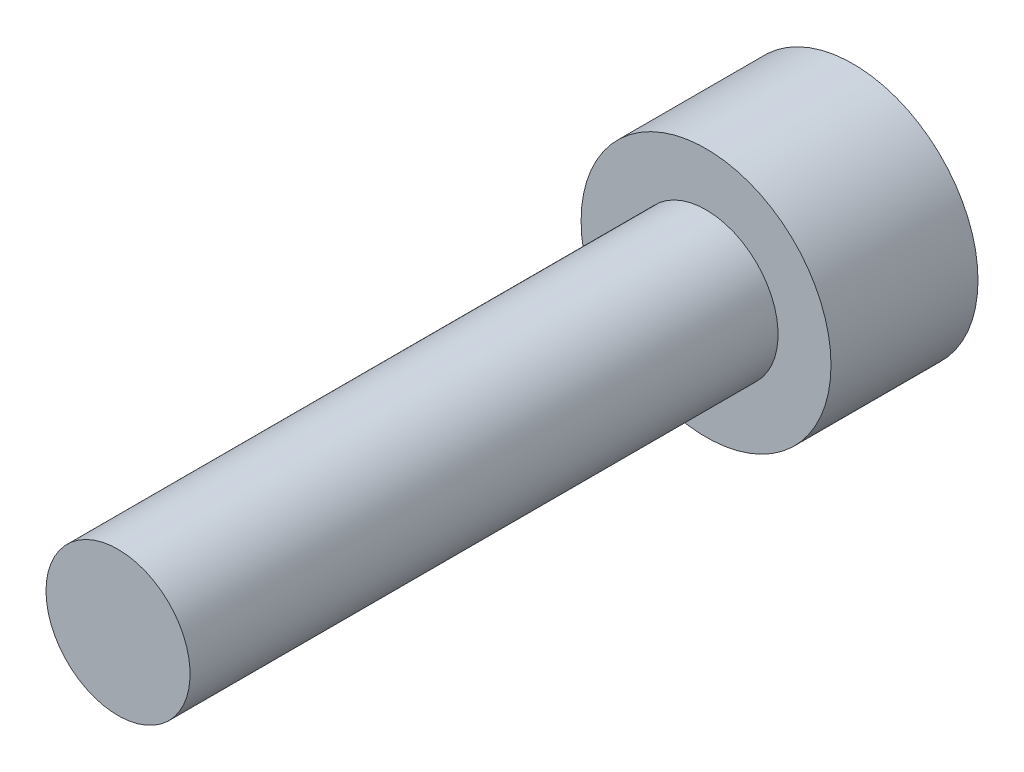
SolidWorks part; units mm, degrees
material "Plain Carbon Steel"
ref_plane "Front Plane" through (0, 0, 0) normal (0, 0, 1) x (1, 0, 0)
ref_plane "Top Plane" through (0, 0, 0) normal (0, 1, 0) x (1, 0, 0)
ref_plane "Right Plane" through (0, 0, 0) normal (1, 0, 0) x (0, 0, -1)
sketch "Sketch1" plane through (0, 0, 0) normal (0, 1, 0) x (1, 0, 0)
  line L0 (0, 33.516) -> (0, 12.152) construction
  line L1 (0, 5) -> (-4.25, 5)
  line L2 (-4.25, 5) -> (-4.25, 0)
  line L3 (-4.25, 0) -> (-2.45, 0)
  line L4 (-2.45, 0) -> (-2.45, -20)
  line L5 (-2.45, -20) -> (0, -20)
  line L6 (-2.45, 0) -> (0, 0) construction
  line L7 (0, 5) -> (0, -20)
  dimension "D1" = 4.9
  dimension "D2" = 8.5
  dimension "D3" = 5
  dimension "D4" = 20
revolve "Revolve1" add sketch "Sketch1" angle 360 about L7
cosmetic thread "Cosmetic Thread1" parameters "D2"=3.22
sketch "Sketch2" plane through (0, 0, -5) normal (0, 0, -1) x (-1, 0, 0)
  line L1 (-1.3337, 2.31) -> (-2.6674, 0)
  line L2 (-2.6674, 0) -> (-1.3337, -2.31)
  line L3 (-1.3337, -2.31) -> (1.3337, -2.31)
  line L4 (1.3337, -2.31) -> (2.6674, 0)
  line L5 (2.6674, 0) -> (1.3337, 2.31)
  line L6 (1.3337, 2.31) -> (-1.3337, 2.31)
  circle A0 centre (0, 0) radius 2.31 construction
  dimension "D1" = 4.62
extrude "Cut-Extrude1" cut sketch "Sketch2" against normal blind 2.5
sketch "Sketch3" plane through (0, 0, 0) normal (0, 1, 0) x (1, 0, 0)
  line L0 (-2.6674, 5) -> (-0.6674, 3)
  line L2 (-0.6674, 3) -> (-0.6674, 5)
  line L3 (4.25, 5) -> (-4.25, 5) construction
  line L4 (-0.6674, 5) -> (-2.6674, 5)
  line L5 (0, 0) -> (0, 5) construction
  dimension "D1" = 45
  dimension "D2" = 2
revolve "Cut-Revolve1" cut sketch "Sketch3" angle 360 about L5
equation "\"length\"= 20mm"
equation "\"D4@Sketch1\"=\"length\""
